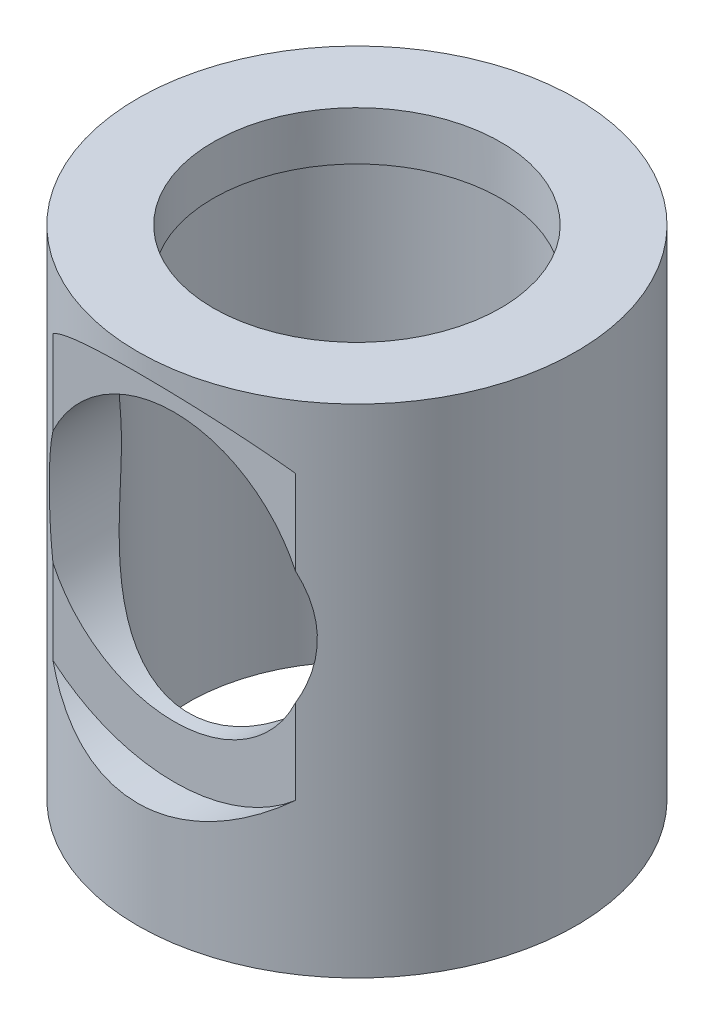
SolidWorks part; units mm, degrees
material "OMD-98"
ref_plane "Front Plane" through (0, 0, 0) normal (0, 0, 1) x (1, 0, 0)
ref_plane "Top Plane" through (0, 0, 0) normal (0, 1, 0) x (1, 0, 0)
ref_plane "Right Plane" through (0, 0, 0) normal (1, 0, 0) x (0, 0, -1)
sketch "Sketch1" plane through (0, 0, 0) normal (0, 1, 0) x (1, 0, 0)
  circle A0 centre (0, 0) radius 9
  circle A1 centre (0, 0) radius 5.9
  dimension "D1" = 18
  dimension "D2" = 11.8
extrude "Boss-Extrude1" add sketch "Sketch1" against normal blind 20.4
sketch "Sketch3" plane through (0, 0, 0) normal (0, 0, 1) x (1, 0, 0)
  line L1 (5.9, 0) -> (-5.9, 0) construction
  circle A0 centre (0, -8.4) radius 7.65
  dimension "D1" = 15.3
  dimension "D2" = 8.4
extrude "Cut-Extrude5" cut sketch "Sketch3" along normal through all from offset 7.5
sketch "Sketch6" plane through (0, 0, 7.5) normal (0, 0, 1) x (1, 0, 0)
  line L2 (9, 0) -> (-9, 0) construction
  circle A0 centre (0, -8.4) radius 5.5
  point P2 (0, 0)
  dimension "D1" = 11
  dimension "D2" = 8.4
extrude "Cut-Extrude6" cut sketch "Sketch6" against normal blind 7 and the other way through all
sketch "Sketch7" plane through (0, -20.4, 0) normal (0, -1, 0) x (1, 0, 0)
  circle A0 centre (0, 0) radius 6.9
  dimension "D1" = 13.8
extrude "Cut-Extrude7" cut sketch "Sketch7" against normal blind 18.4
